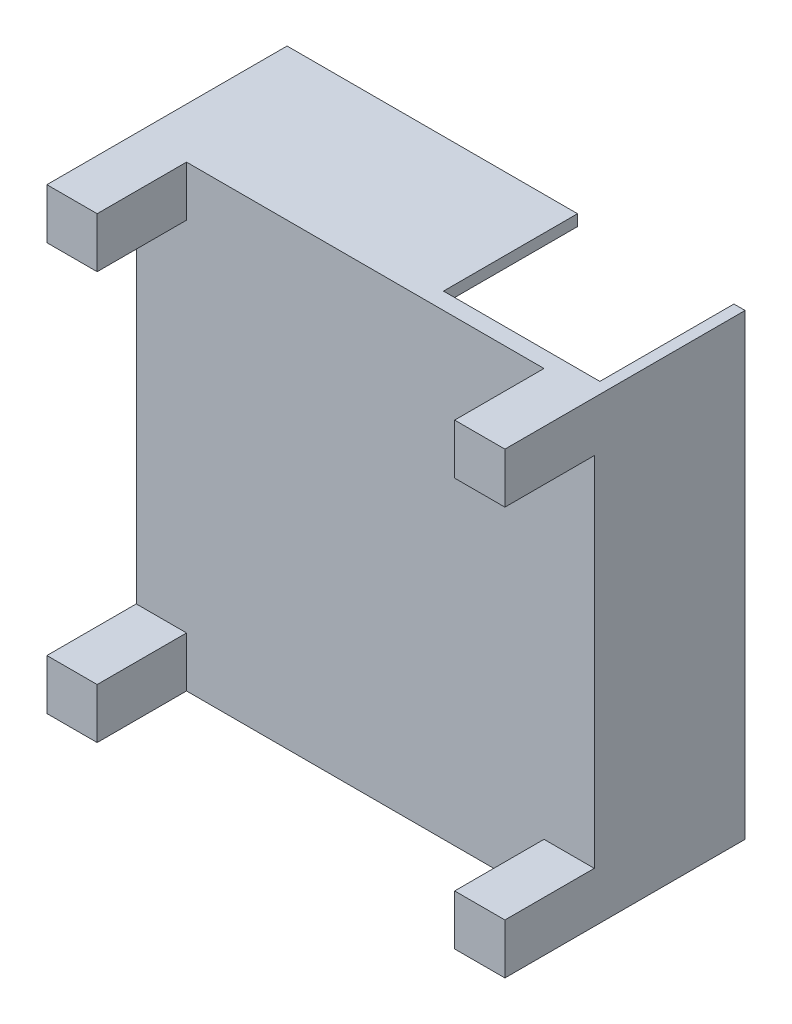
SolidWorks part; units mm, degrees
ref_plane "Piano frontale" through (0, 0, 0) normal (0, 0, 1) x (1, 0, 0)
ref_plane "Piano superiore" through (0, 0, 0) normal (0, 1, 0) x (1, 0, 0)
ref_plane "Piano destro" through (0, 0, 0) normal (1, 0, 0) x (0, 0, -1)
sketch "Schizzo1" plane through (0, 0, 0) normal (0, 0, 1) x (1, 0, 0)
  line L1 (0, 0) -> (41, 0)
  line L2 (0, 0) -> (0, 41)
  line L3 (0, 41) -> (41, 41)
  line L4 (41, 0) -> (41, 41)
  dimension "D1" = 41
  dimension "D2" = 41
extrude "Estrusione-Estrusione1" add sketch "Schizzo1" along normal blind 1.5 contours L1 L4 L3 L2
sketch "Schizzo5" plane through (0, 0, 1.5) normal (0, 0, 1) x (1, 0, 0)
  line L1 (0, 0) -> (4.5, 0)
  line L2 (0, 0) -> (0, 4.5)
  line L3 (0, 4.5) -> (4.5, 4.5)
  line L4 (4.5, 0) -> (4.5, 4.5)
  dimension "D1" = 4.5
  dimension "D2" = 4.5
extrude "Estrusione-Estrusione2" add sketch "Schizzo5" along normal blind 8
sketch "Schizzo6" plane through (0, 0, 1.5) normal (0, 0, 1) x (1, 0, 0)
  line L1 (41, 0) -> (36.5, 0)
  line L2 (41, 0) -> (41, 4.5)
  line L3 (41, 4.5) -> (36.5, 4.5)
  line L4 (36.5, 0) -> (36.5, 4.5)
  dimension "D1" = 4.5
  dimension "D2" = 4.5
extrude "Estrusione-Estrusione3" add sketch "Schizzo6" along normal blind 8
sketch "Schizzo7" plane through (0, 0, 1.5) normal (0, 0, 1) x (1, 0, 0)
  line L1 (0, 41) -> (4.5, 41)
  line L2 (0, 41) -> (0, 36.5)
  line L3 (0, 36.5) -> (4.5, 36.5)
  line L4 (4.5, 41) -> (4.5, 36.5)
  dimension "D1" = 4.5
  dimension "D2" = 4.5
extrude "Estrusione-Estrusione4" add sketch "Schizzo7" along normal blind 8
sketch "Schizzo8" plane through (0, 0, 1.5) normal (0, 0, 1) x (1, 0, 0)
  line L1 (41, 41) -> (36.5, 41)
  line L2 (41, 41) -> (41, 36.5)
  line L3 (41, 36.5) -> (36.5, 36.5)
  line L4 (36.5, 41) -> (36.5, 36.5)
  dimension "D1" = 4.5
  dimension "D2" = 4.5
extrude "Estrusione-Estrusione5" add sketch "Schizzo8" along normal blind 8
sketch "Schizzo9" plane through (0, 0, 0) normal (0, 0, -1) x (-1, 0, 0)
  line L0 (0, 0) -> (-41, 0) construction
  line L1 (-41, 41) -> (-40, 41)
  line L2 (-41, 41) -> (-41, 0)
  line L3 (-41, 0) -> (-40, 0)
  line L4 (-40, 41) -> (-40, 0)
  dimension "D1" = 1
  dimension "D2" = 41
extrude "Estrusione-Estrusione6" add sketch "Schizzo9" along normal blind 12
sketch "Schizzo10" plane through (0, 0, 0) normal (0, 0, -1) x (-1, 0, 0)
  line L0 (0, 41) -> (-40, 41) construction
  line L1 (-26, 41) -> (0, 41)
  line L2 (-26, 41) -> (-26, 40)
  line L3 (-26, 40) -> (0, 40)
  line L4 (0, 41) -> (0, 40)
  line L5 (0, 0) -> (0, 41) construction
  dimension "D1" = 26
  dimension "D2" = 1
extrude "Estrusione-Estrusione7" add sketch "Schizzo10" along normal blind 12
